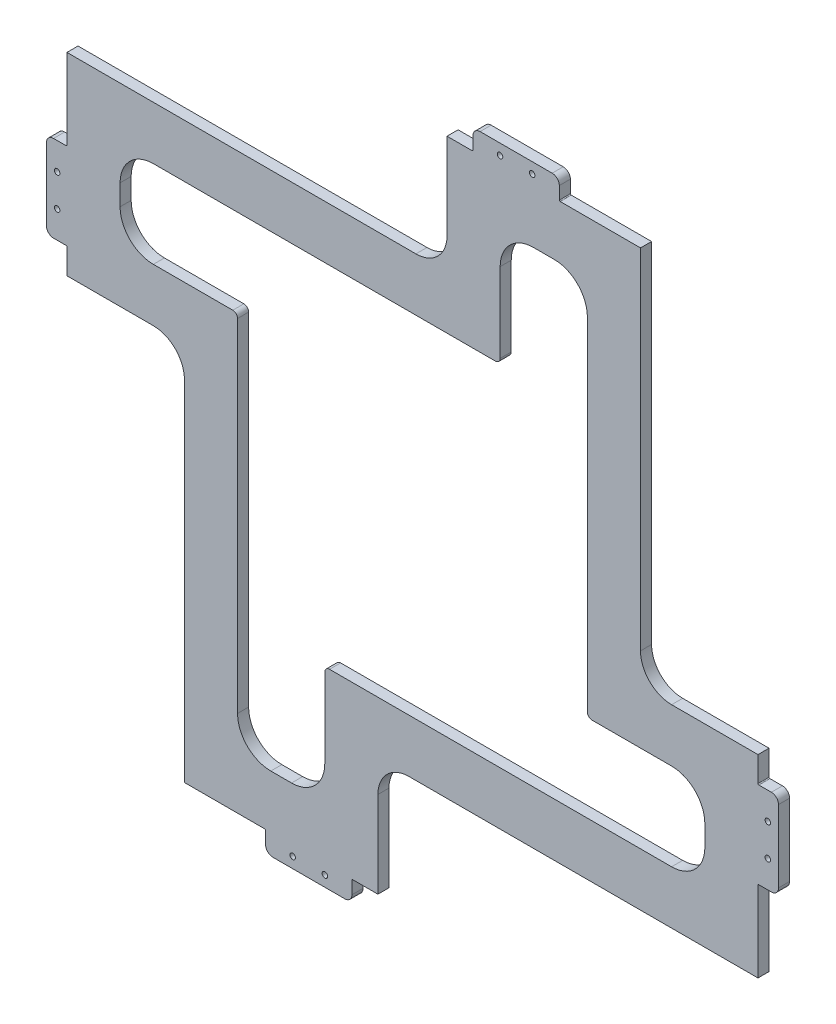
SolidWorks part; units mm, degrees
ref_plane "front" through (0, 0, 0) normal (0, 0, 1) x (1, 0, 0)
ref_plane "top" through (0, 0, 0) normal (0, 1, 0) x (1, 0, 0)
ref_plane "right" through (0, 0, 0) normal (1, 0, 0) x (0, 0, -1)
ref_axis "Axis1" through (0, 0, -69.7337) along (0, 0, 1)
sketch "Sketch1" plane through (0, 0, 0) normal (0, 0, 1) x (1, 0, 0)
  line L0 (-24.572, 24.572) -> (24.572, 24.572)
  line L1 (24.572, 24.572) -> (24.572, -24.572)
  line L2 (24.572, -24.572) -> (-24.572, -24.572)
  line L3 (-24.572, -24.572) -> (-24.572, 24.572)
  line L4 (-24.572, 0) -> (-280.8588, 0) construction
  line L5 (-280.8588, 0) -> (0, 49.523)
  line L6 (-280.8588, 0) -> (0, 24.572)
  dimension "D1" = 10
  dimension "D2" = 5
  dimension "D3" = 280.8588
  dimension "D4" = 285.1915
  dimension "A" = 49.1439
sketch "Sketch2" plane through (0, 0, 0) normal (0, 0, 1) x (1, 0, 0)
  line L0 (-19.6576, 24.572) -> (11.7945, 24.572)
  line L1 (-24.572, 24.572) -> (24.572, 24.572) construction
  line L2 (12.7774, 25.5548) -> (12.7774, 36.8579)
  line L3 (24.572, 36.8579) -> (24.572, 9.8288)
  line L4 (24.572, 9.8288) -> (32.435, 9.8288)
  line L5 (32.435, 9.8288) -> (32.435, 49.1439)
  line L6 (8.4732, 49.1439) -> (4.9144, 49.1439)
  line L7 (4.9144, 36.8579) -> (12.7774, 36.8579) construction
  line L8 (4.9144, 49.1439) -> (4.9144, 36.8579)
  line L10 (32.435, 49.1439) -> (21.0132, 49.1439)
  line L11 (20.8862, 49.2709) -> (20.8862, 51.0489)
  line L12 (19.8702, 52.0649) -> (9.6162, 52.0649)
  line L13 (8.6002, 51.0489) -> (8.6002, 49.2709)
  line L14 (0.4914, 32.435) -> (-19.6576, 32.435)
  line L15 (-19.6576, 32.435) -> (-19.6576, 24.572)
  line L16 (24.572, 24.572) -> (24.572, -24.572) construction
  line L18 (17.2004, 41.2809) -> (20.149, 41.2809)
  arc A0 (4.9144, 36.8579) -> (0.4914, 32.435) centre (0.4914, 36.8579) cw
  arc A1 (9.6162, 52.0649) -> (8.6002, 51.0489) centre (9.6162, 51.0489) ccw
  arc A2 (20.8862, 51.0489) -> (19.8702, 52.0649) centre (19.8702, 51.0489) ccw
  arc A3 (8.6002, 49.2709) -> (8.4732, 49.1439) centre (8.4732, 49.2709) cw
  circle A4 centre (12.4572, 50.5409) radius 0.3937
  arc A5 (21.0132, 49.1439) -> (20.8862, 49.2709) centre (21.0132, 49.2709) cw
  circle A6 centre (17.0292, 50.5409) radius 0.3937
  arc A9 (20.149, 41.2809) -> (24.572, 36.8579) centre (20.149, 36.8579) cw
  arc A10 (12.7774, 36.8579) -> (17.2004, 41.2809) centre (17.2004, 36.8579) cw
  arc A11 (11.7945, 24.572) -> (12.7774, 25.5548) centre (11.7945, 25.5548) ccw
  point P16 (14.7432, 52.0649)
  dimension "D9" = 0.9829
  dimension "D6" = 0.127
  dimension "D2" = 24.572
  dimension "D5" = 12.286
  dimension "D8" = 7.863
  dimension "D10" = 7.863
  dimension "D12" = 19.6576
  dimension "D13" = 9.8288
  dimension "D4" = 4.9144
  dimension "D15" = 27.5206
  dimension "D11" = 14.7432
  dimension "D16" = 2.286
  dimension "D17" = 2.286
extrude "Extrude1" add sketch "Sketch2" against normal mid plane 1.5748
pattern_circular "CirPattern1" count 4 over 360 about axis through (0, 0, -69.7337) along (0, 0, 1) of "Extrude1"
sketch "Sketch3" plane through (0, 0, 0.7874) normal (0, 0, 1) x (1, 0, 0)
  line L156 (-41.5857, 20.149) -> (-41.5857, 17.2004)
  line L157 (-36.8579, 12.4726) -> (-25.5548, 12.4726)
  line L158 (-24.8768, 11.7945) -> (-24.8768, -36.8579)
  line L159 (-20.149, -41.5857) -> (-17.2004, -41.5857)
  line L160 (-12.4726, -36.8579) -> (-12.4726, -25.5548)
  line L161 (-11.7945, -24.8768) -> (36.8579, -24.8768)
  line L162 (41.5857, -20.149) -> (41.5857, -17.2004)
  line L163 (36.8579, -12.4726) -> (25.5548, -12.4726)
  line L164 (24.8768, -11.7945) -> (24.8768, 36.8579)
  line L165 (20.149, 41.5857) -> (17.2004, 41.5857)
  line L166 (12.4726, 36.8579) -> (12.4726, 25.5548)
  line L167 (11.7945, 24.8768) -> (-36.8579, 24.8768)
  line L168 (-41.5857, 20.149) -> (-41.5857, 17.2004)
  line L169 (-36.8579, 12.4726) -> (-25.5548, 12.4726)
  line L170 (-24.8768, 11.7945) -> (-24.8768, -36.8579)
  line L171 (-20.149, -41.5857) -> (-17.2004, -41.5857)
  line L172 (-12.4726, -36.8579) -> (-12.4726, -25.5548)
  line L173 (-11.7945, -24.8768) -> (36.8579, -24.8768)
  line L174 (41.5857, -20.149) -> (41.5857, -17.2004)
  line L175 (36.8579, -12.4726) -> (25.5548, -12.4726)
  line L176 (24.8768, -11.7945) -> (24.8768, 36.8579)
  line L177 (20.149, 41.5857) -> (17.2004, 41.5857)
  line L178 (12.4726, 36.8579) -> (12.4726, 25.5548)
  line L179 (11.7945, 24.8768) -> (-36.8579, 24.8768)
  arc A168 (-41.5857, 17.2004) -> (-36.8579, 12.4726) centre (-36.8579, 17.2004) ccw
  arc A169 (-24.8768, 11.7945) -> (-25.5548, 12.4726) centre (-25.5548, 11.7945) ccw
  arc A170 (-24.8768, -36.8579) -> (-20.149, -41.5857) centre (-20.149, -36.8579) ccw
  arc A171 (-17.2004, -41.5857) -> (-12.4726, -36.8579) centre (-17.2004, -36.8579) ccw
  arc A172 (-11.7945, -24.8768) -> (-12.4726, -25.5548) centre (-11.7945, -25.5548) ccw
  arc A173 (36.8579, -24.8768) -> (41.5857, -20.149) centre (36.8579, -20.149) ccw
  arc A174 (41.5857, -17.2004) -> (36.8579, -12.4726) centre (36.8579, -17.2004) ccw
  arc A175 (24.8768, -11.7945) -> (25.5548, -12.4726) centre (25.5548, -11.7945) ccw
  arc A176 (24.8768, 36.8579) -> (20.149, 41.5857) centre (20.149, 36.8579) ccw
  arc A177 (17.2004, 41.5857) -> (12.4726, 36.8579) centre (17.2004, 36.8579) ccw
  arc A178 (11.7945, 24.8768) -> (12.4726, 25.5548) centre (11.7945, 25.5548) ccw
  arc A179 (-36.8579, 24.8768) -> (-41.5857, 20.149) centre (-36.8579, 20.149) ccw
  arc A180 (-41.5857, 17.2004) -> (-36.8579, 12.4726) centre (-36.8579, 17.2004) ccw
  arc A181 (-24.8768, 11.7945) -> (-25.5548, 12.4726) centre (-25.5548, 11.7945) ccw
  arc A182 (-24.8768, -36.8579) -> (-20.149, -41.5857) centre (-20.149, -36.8579) ccw
  arc A183 (-17.2004, -41.5857) -> (-12.4726, -36.8579) centre (-17.2004, -36.8579) ccw
  arc A184 (-11.7945, -24.8768) -> (-12.4726, -25.5548) centre (-11.7945, -25.5548) ccw
  arc A185 (36.8579, -24.8768) -> (41.5857, -20.149) centre (36.8579, -20.149) ccw
  arc A186 (41.5857, -17.2004) -> (36.8579, -12.4726) centre (36.8579, -17.2004) ccw
  arc A187 (24.8768, -11.7945) -> (25.5548, -12.4726) centre (25.5548, -11.7945) ccw
  arc A188 (24.8768, 36.8579) -> (20.149, 41.5857) centre (20.149, 36.8579) ccw
  arc A189 (17.2004, 41.5857) -> (12.4726, 36.8579) centre (17.2004, 36.8579) ccw
  arc A190 (11.7945, 24.8768) -> (12.4726, 25.5548) centre (11.7945, 25.5548) ccw
  arc A191 (-36.8579, 24.8768) -> (-41.5857, 20.149) centre (-36.8579, 20.149) ccw
  dimension "D1" = 0.3048
extrude "Cut-Extrude1" cut sketch "Sketch3" against normal blind 2.54
sketch "Sketch4" plane through (0, 0, 0.7874) normal (0, 0, 1) x (1, 0, 0)
  line L0 (-24.8768, 11.7945) -> (-24.8768, -36.8579) construction
  line L1 (-24.8768, -24.8768) -> (24.8768, -24.8768)
  line L2 (-24.8768, -24.8768) -> (-24.8768, 24.8768)
  line L3 (-24.8768, 24.8768) -> (24.8768, 24.8768)
  line L4 (24.8768, -24.8768) -> (24.8768, 24.8768)
  line L5 (11.7945, 24.8768) -> (-36.8579, 24.8768) construction
  line L6 (24.8768, -11.7945) -> (24.8768, 36.8579) construction
  line L7 (-11.7945, -24.8768) -> (36.8579, -24.8768) construction
sketch "Sketch5" plane through (0, 0, 0.7874) normal (0, 0, 1) x (1, 0, 0)
  line L0 (-36.8579, 12.4726) -> (-25.5548, 12.4726) construction
  line L1 (12.4726, 36.8579) -> (12.4726, 25.5548) construction
  line L2 (36.8579, -12.4726) -> (25.5548, -12.4726) construction
  line L3 (-12.4726, -36.8579) -> (-12.4726, -25.5548) construction
  line L4 (-41.5857, 20.149) -> (-41.5857, 17.2004) construction
  line L5 (20.149, 41.5857) -> (17.2004, 41.5857) construction
  line L6 (41.5857, -20.149) -> (41.5857, -17.2004) construction
  line L7 (-20.149, -41.5857) -> (-17.2004, -41.5857) construction
  circle A0 centre (-36.5057, 18.6702) radius 2.0193
  circle A1 centre (18.6702, 36.5057) radius 2.0193
  circle A2 centre (36.5057, -18.6702) radius 2.0193
  circle A3 centre (-18.6702, -36.5057) radius 2.0193
  point P20 (18.6747, 41.5857)
  point P25 (-18.6747, -41.5857)
  dimension "D1" = 6.1976
  dimension "D9" = 4.0386
  dimension "D2" = 6.1976
  dimension "D3" = 6.1976
  dimension "D4" = 6.1976
  dimension "D5" = 5.08
  dimension "D6" = 5.08
  dimension "D7" = 5.08
  dimension "D8" = 5.08
sketch "Sketch6" plane through (0, 0, 0.7874) normal (0, 0, 1) x (1, 0, 0)
  line L0 (-49.1439, 32.435) -> (-49.1439, 4.9144)
  line L1 (4.9144, 49.1439) -> (32.435, 49.1439)
  line L3 (49.1439, -4.9144) -> (49.1439, -32.435)
  line L5 (-4.9144, -49.1439) -> (-32.435, -49.1439)
equation "\"D2@Sketch2\" = .5 * \"A\""
equation "\"D13@Sketch2\" = .2 * \"A\""
equation "\"D8@Sketch2\" = .16 * \"A\""
equation "\"D10@Sketch2\" = .16 * \"A\""
equation "\"D5@Sketch2\" = .25 * \"A\""
equation "\"D12@Sketch2\" = .4 * \"A\""
equation "\"D4@Sketch2\"=.1*\"A\""
equation "\"D9@Sketch2\"=.02*\"A\""
equation "\"D11@Sketch2\"=.3*\"A\""
